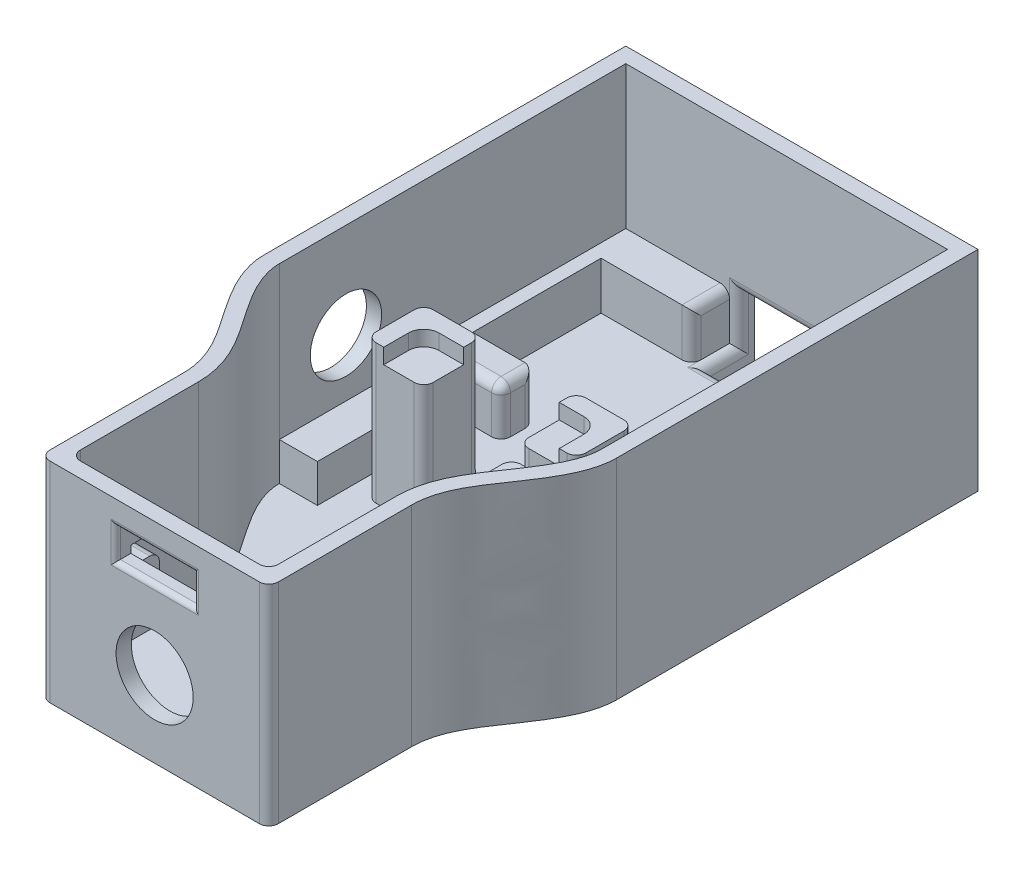
SolidWorks part; units mm, degrees
material "Melamine resin"
ref_plane "Front Plane" through (0, 0, 0) normal (0, 0, 1) x (1, 0, 0)
ref_plane "Top Plane" through (0, 0, 0) normal (0, 1, 0) x (1, 0, 0)
ref_plane "Right Plane" through (0, 0, 0) normal (1, 0, 0) x (0, 0, -1)
sketch "Sketch1" plane through (0, 0, 0) normal (0, 1, 0) x (1, 0, 0)
  line L0 (-18.5, 68) -> (0, 68)
  line L9 (0, 68) -> (0, 0)
  line L10 (-18.5, 68) -> (-18.5, 30)
  line L11 (0, 0) -> (-12, 0)
  line L12 (-12, 0) -> (-12, 15)
  line L13 (-18.5, 30) -> (-12, 30) construction
  line L14 (-12, 30) -> (-12, 15) construction
  line L15 (-15.25, 22.5) -> (-12, 22.5) construction
  line L16 (0, 1.6) -> (-10.4, 1.6)
  line L17 (-15.25, 30) -> (-15.25, 22.5) construction
  line L18 (-10.4, 1.6) -> (-10.4, 15)
  line L19 (-16.9, 66.4) -> (-16.9, 30)
  line L20 (-16.9, 66.4) -> (0, 66.4)
  line L21 (0, 68) -> (0, 66.4)
  line L22 (0, 1.6) -> (0, 0)
  spline S0 degree 3 poles (-18.5, 30) (-18.5, 27.3947) (-15.25, 22.3602) (-12, 17.8849) (-12, 15) knots 0 0 0 0 0.5 1 1 1 1
  spline S1 degree 1 poles (-16.9, 30) (-10.4, 15) knots 0 0 1 1 construction
  spline S2 degree 3 poles (-10.4, 15) (-10.4, 15.4256) (-10.4616, 16.2904) (-10.7983, 17.8861) (-11.54, 19.6983) (-12.6996, 21.6224) (-13.9392, 23.4086) (-15.1181, 25.1604) (-16.1016, 26.879) (-16.6415, 28.2398) (-16.8623, 29.268) (-16.9, 29.7529) (-16.9, 30) knots 0 0 0 0 0.0625 0.125 0.25 0.375 0.5 0.625 0.75 0.875 0.9375 1 1 1 1
  dimension "D1" = 18.5
  dimension "D2" = 68
  dimension "D3" = 15
  dimension "D4" = 15
  dimension "D5" = 12
  dimension "D6" = 1.6
extrude "Boss-Extrude1" add sketch "Sketch1" against normal blind 2 contours S0 L12 L11 L9 L0 L10
extrude "Boss-Extrude2" add sketch "Sketch1<3>" along normal blind 20 contours L18 S2 L19 L20 L9 L0 L10 S0 L12 L11 L16 region at (-9.25, 0, -67.2953)
sketch "Sketch1<3>" plane through (0, 0, 0) normal (0, 1, 0) x (1, 0, 0) same geometry as "Sketch1"
fillet "Fillet1" radius 1 2 edges at (-10.4, 10, -1.6) (-12, 9, 0)
mirror "Mirror1" about plane through (0, 0, 0) normal (1, 0, 0) of "Boss-Extrude2", "Fillet1", "Boss-Extrude1"
sketch "Sketch2" plane through (0, 0, 0) normal (0, 0, 1) x (1, 0, 0)
  line L0 (0, 0) -> (0, 6) construction
  line L1 (0, 6) -> (0, 15.84) construction
  line L2 (4.1, 14.24) -> (-4.1, 14.24)
  line L3 (4.1, 14.24) -> (4.1, 17.44)
  line L4 (4.1, 17.44) -> (-4.1, 17.44)
  line L5 (-4.1, 14.24) -> (-4.1, 17.44)
  line L6 (4.1, 14.24) -> (-4.1, 17.44) construction
  line L7 (4.1, 17.44) -> (-4.1, 14.24) construction
  line L8 (11, 20) -> (-11, 20) construction
  circle A0 centre (0, 6) radius 4.05
  point P4 (0, 15.84)
  dimension "D1" = 8.1
  dimension "D2" = 6
  dimension "D3" = 8.2
  dimension "D4" = 3.2
  dimension "D5" = 4.16
extrude "Cut-Extrude1" cut sketch "Sketch2" against normal up to next
sketch "Sketch3" plane through (0, 0, 0) normal (0, 1, 0) x (1, 0, 0)
  line L0 (-15.5, 55.65) -> (15.5, 55.65) construction
  line L1 (-16.9, 66.4) -> (-6, 66.4)
  line L2 (-16.9, 66.4) -> (-16.9, 45.4)
  line L3 (-16.9, 45.4) -> (-9, 45.4)
  line L4 (16.9, 66.4) -> (16.9, 45.4)
  line L5 (9, 45.4) -> (16.9, 45.4)
  line L7 (-9, 48.9) -> (-9, 45.4)
  line L9 (9, 48.9) -> (9, 45.4)
  line L10 (9, 48.9) -> (15.5, 48.9)
  line L11 (-15.5, 62.4) -> (-6, 62.4)
  line L12 (-15.5, 62.4) -> (-15.5, 48.9)
  line L13 (-15.5, 48.9) -> (-9, 48.9)
  line L14 (15.5, 62.4) -> (15.5, 48.9)
  line L15 (-9, 45.4) -> (9, 45.4) construction
  line L16 (-9, 48.9) -> (9, 48.9) construction
  line L17 (0, 66.4) -> (0, 62.4) construction
  line L18 (0, 62.4) -> (0, 48.9) construction
  line L19 (0, 48.9) -> (0, 45.4) construction
  line L20 (16.9, 66.4) -> (16.9, 30) construction
  line L21 (-6, 62.4) -> (-6, 66.4)
  line L22 (6, 62.4) -> (6, 66.4)
  line L23 (6, 62.4) -> (15.5, 62.4)
  line L24 (6, 66.4) -> (16.9, 66.4)
  line L25 (-6, 66.4) -> (6, 66.4) construction
  line L26 (-16.9, 66.4) -> (16.9, 66.4) construction
  line L27 (-6, 62.4) -> (6, 62.4) construction
  point P23 (0, 55.65)
  dimension "D1" = 31
  dimension "D2" = 13.5
  dimension "D3" = 12
  dimension "D4" = 4
  dimension "D5" = 18
  dimension "D6" = 3.5
extrude "Boss-Extrude3" add sketch "Sketch3" along normal blind 5
ref_plane "IR_mid" through (0, 0, -55.65) normal (0, 0, 1) x (1, 0, 0)
sketch "Sketch4" plane through (0, 0, -68) normal (0, 0, -1) x (-1, 0, 0)
  line L0 (18.5, -2) -> (-18.5, -2) construction
  line L1 (-5, -2) -> (5, -2)
  line L2 (-5, -2) -> (-5, 5)
  line L3 (-5, 5) -> (5, 5)
  line L4 (5, -2) -> (5, 5)
  line L5 (0, 5) -> (0, -2) construction
  dimension "D1" = 10
  dimension "D2" = 7
extrude "Cut-Extrude2" cut sketch "Sketch4" against normal blind 5
sketch "Sketch5" plane through (-18.5, 0, 0) normal (-1, 0, 0) x (0, 0, 1)
  line L0 (-37, 20) -> (-37, 0) construction
  line L1 (-68, 20) -> (-30, 20) construction
  line L2 (-37, 0) -> (0, 0) construction
  circle A0 centre (-37, 10) radius 3.75
  dimension "D1" = 7.5
  dimension "D2" = 37
extrude "Cut-Extrude3" cut sketch "Sketch5" against normal up to next
sketch "Sketch6" plane through (0, 0, 0) normal (0, 1, 0) x (1, 0, 0)
  line L0 (-16.9, 45.4) -> (-16.9, 30) construction
  line L1 (-16.9, 45.4) -> (-12.9, 45.4)
  line L2 (-16.9, 45.4) -> (-16.9, 30)
  line L3 (-16.9, 30) -> (-12.9, 30)
  line L4 (-12.9, 45.4) -> (-12.9, 30)
  spline S0 degree 3 poles (-10.4, 15) (-10.4, 15.4256) (-10.4616, 16.2904) (-10.7983, 17.8861) (-11.54, 19.6983) (-12.6996, 21.6224) (-13.9392, 23.4086) (-15.1181, 25.1604) (-16.1016, 26.879) (-16.6415, 28.2398) (-16.8623, 29.268) (-16.9, 29.7529) (-16.9, 30) knots 0 0 0 0 0.0625 0.125 0.25 0.375 0.5 0.625 0.75 0.875 0.9375 1 1 1 1 construction
  dimension "D1" = 4
extrude "Boss-Extrude4" add sketch "Sketch6" along normal blind 4
sketch "Sketch7" plane through (0, 0, -1.6) normal (0, 0, -1) x (-1, 0, 0)
  line L0 (4.1, 13) -> (9, 13)
  line L1 (11.1, 11) -> (4.1, 11)
  line L4 (4.1, 11) -> (4.1, 13)
  line L5 (9, 13) -> (9, 15)
  line L10 (4.1, 11) -> (0, 11) construction
  line L11 (9, 15) -> (4.1, 15)
  line L12 (-9.4, 0) -> (9.4, 0) construction
  line L13 (0, 0) -> (0, 11) construction
  line L14 (4.1, 15) -> (4.1, 17)
  line L15 (4.1, 17) -> (11.1, 17)
  line L16 (11.1, 11) -> (11.1, 17)
  line L17 (4.1, 13) -> (4.1, 15) construction
  dimension "D1" = 7
  dimension "D2" = 2
  dimension "D3" = 11
  dimension "D4" = 4.1
  dimension "D5" = 2
  dimension "D6" = 9
extrude "Boss-Extrude5" add sketch "Sketch7" along normal blind 3
sketch "Sketch9" plane through (0, 0, 0) normal (0, 1, 0) x (1, 0, 0)
  line L0 (0, 0) -> (0, 36.788) construction
  line L1 (-5.018, 33.288) -> (-11.018, 33.288)
  line L2 (-5.018, 33.288) -> (-5.018, 39.288)
  line L3 (-5.018, 39.288) -> (-11.018, 39.288)
  line L4 (-11.018, 33.288) -> (-11.018, 39.288)
  line L5 (-8.518, 36.788) -> (-8.518, 39.288) construction
  line L6 (-8.518, 36.788) -> (-11.018, 36.788) construction
  line L7 (0, 36.788) -> (-8.518, 36.788) construction
  point P0 (-8.518, 36.788)
  dimension "D1" = 2.5
  dimension "D2" = 2.5
  dimension "D3" = 8.518
  dimension "D4" = 36.788
  dimension "D5" = 6
  dimension "D6" = 6
extrude "Boss-Extrude7" add sketch "Sketch9" along normal up to surface (13 mm away) up to face at (-6.55, 13, -3.1)
sketch "Sketch10" plane through (0, 13, 0) normal (0, 1, 0) x (1, 0, 0)
  line L0 (-11.018, 39.288) -> (-11.018, 33.288)
  line L1 (-11.018, 33.288) -> (-11.018, 39.288) construction
  line L2 (-5.018, 33.288) -> (-11.018, 33.288) construction
  line L3 (-11.018, 33.288) -> (-9.218, 33.288)
  line L4 (-9.218, 33.288) -> (-9.218, 37.488) construction
  line L5 (-9.218, 37.488) -> (-5.018, 37.488) construction
  line L6 (-5.018, 39.288) -> (-5.018, 33.288) construction
  line L7 (-5.018, 37.488) -> (-5.018, 39.288)
  line L8 (-5.018, 39.288) -> (-11.018, 39.288)
  line L10 (-11.018, 39.288) -> (-5.018, 39.288) construction
  line L11 (-5.018, 37.488) -> (-7.618, 37.488)
  line L12 (-9.218, 33.288) -> (-9.218, 35.888)
  arc A0 (-9.218, 35.888) -> (-7.618, 37.488) centre (-7.618, 35.888) cw
  dimension "D2" = 1.6
  dimension "D1" = 1.8
extrude "Boss-Extrude8" add sketch "Sketch10" along normal blind 1.6
mirror "Mirror2" about plane through (0, 0, 0) normal (1, 0, 0) of "Boss-Extrude8", "Boss-Extrude5", "Boss-Extrude7"
sketch "Sketch11" plane through (0, 0, 0) normal (0, 1, 0) x (1, 0, 0)
  line L1 (5, 42.488) -> (-5, 42.488)
  line L2 (5, 42.488) -> (5, 37.488)
  line L3 (5, 37.488) -> (-5, 37.488)
  line L4 (-5, 42.488) -> (-5, 37.488)
  line L5 (5, 42.488) -> (-5, 37.488) construction
  line L6 (5, 37.488) -> (-5, 42.488) construction
  circle A0 centre (0, 39.988) radius 1.25 construction
  point P0 (0, 39.988)
  point P5 (0, 0)
  point P6 (0, 39.6936)
  point P7 (0, 40.0635)
  point P8 (0.53, 39.8944)
  point P11 (0, 0)
  dimension "D1" = 10
  dimension "D2" = 5
extrude "Boss-Extrude9" add sketch "Sketch11" along normal blind 1.95
fillet "Fillet2" radius 1 28 edges at (-6, 2.5, -62.4) (-9, 2.5, -48.9) (-11.018, 7.3, -33.288) (-11.018, 7.3, -39.288) (-5, 0.975, -42.488) (-9, 2.5, -45.4) (0, 5, -66.4) (5, 2.5, -66.4) (-5, 2.5, -66.4) (-5, 0, -64.7) (5, 0, -64.7) (0, 0, -63) (6, 2.5, -62.4) (9, 2.5, -45.4) (9, 2.5, -48.9) (11.018, 7.3, -33.288) (11.018, 7.3, -39.288) (5, 0.975, -42.488) (5.018, 6.5, -33.288) (-5.018, 6.5, -33.288) (5.018, 7.3, -39.288) (-5.018, 7.3, -39.288) (6, 5, -64.4) (-6, 5, -64.4) (-9, 5, -47.15) (9, 5, -47.15) (-12.95, 5, -45.4) (12.95, 5, -45.4)
sketch "Sketch12" plane through (0, 1.95, 0) normal (0, 1, 0) x (1, 0, 0)
  circle A0 centre (0, 39.988) radius 1.7
  dimension "D1" = 3.4
extrude "Cut-Extrude4" cut sketch "Sketch12" against normal up to next
chamfer "Chamfer1" distance 1.8 angle 45 1 edges at (0, -2, -41.688)
fillet "Fillet3" radius 0.5 1 edges at (0, -0.2, -41.688)
chamfer "Chamfer2" distance 1.95 angle 45 6 edges at (0, 0, -37.488) (-5, 0, -39.488) (-4.7071, 0, -42.1951) (5, 0, -39.488) (4.7071, 0, -42.1951) (0, 0, -42.488)
fillet "Fillet4" radius 0.5 4 edges at (4.1, 15.84, 0) (0, 14.24, 0) (0, 17.44, 0) (-4.1, 15.84, 0)
fillet "Fillet5" radius 1 6 edges at (9, 14, -4.6) (6.55, 13, -4.6) (6.55, 15, -4.6) (-6.55, 13, -4.6) (-9, 14, -4.6) (-6.55, 15, -4.6)
